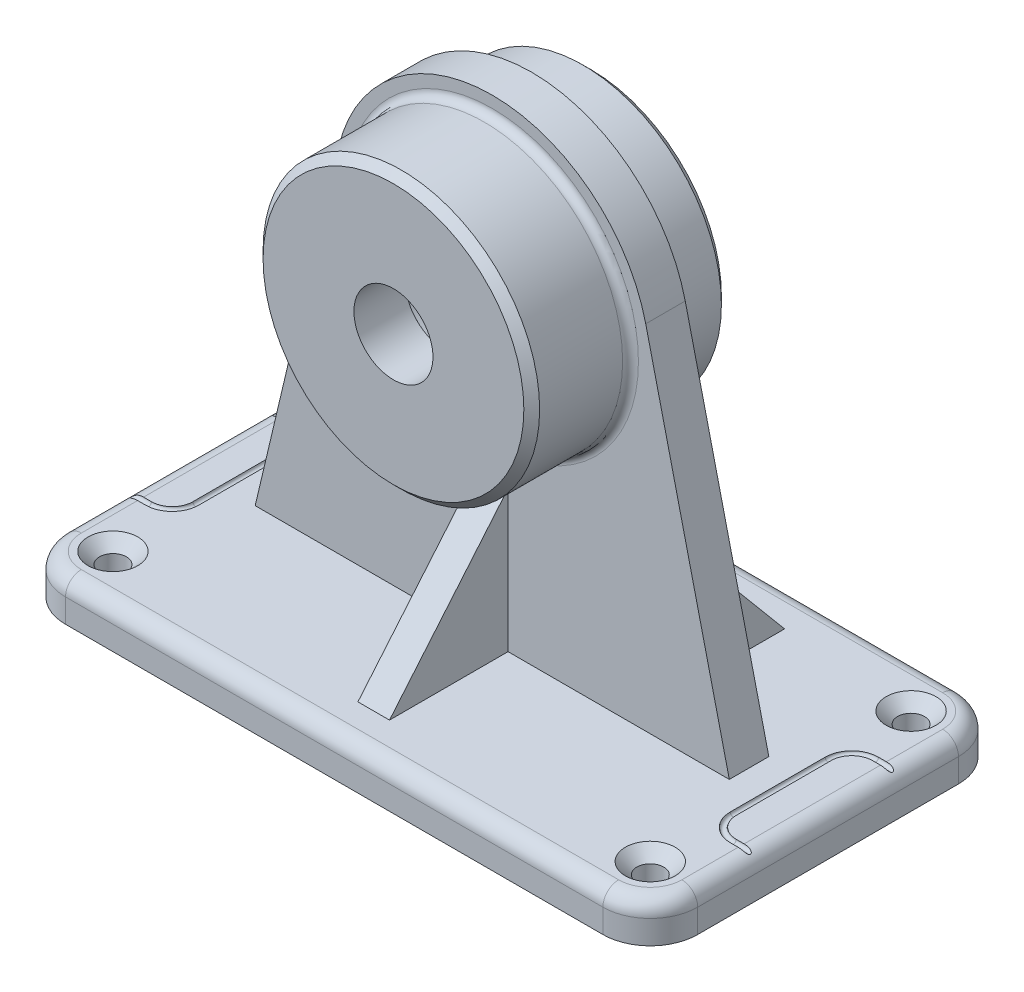
SolidWorks part; units mm, degrees
ref_plane "Front Plane" through (0, 0, 0) normal (0, 0, 1) x (1, 0, 0)
ref_plane "Top Plane" through (0, 0, 0) normal (0, 1, 0) x (1, 0, 0)
ref_plane "Right Plane" through (0, 0, 0) normal (1, 0, 0) x (0, 0, -1)
sketch "Sketch1" plane through (0, 0, 0) normal (0, 1, 0) x (1, 0, 0)
  line L1 (40, -22.5) -> (-40, -22.5)
  line L2 (40, -22.5) -> (40, 22.5)
  line L3 (40, 22.5) -> (-40, 22.5)
  line L4 (-40, -22.5) -> (-40, 22.5)
  line L5 (40, -22.5) -> (-40, 22.5) construction
  line L6 (40, 22.5) -> (-40, -22.5) construction
  point P0 (0, 0)
  dimension "D1" = 80
  dimension "D2" = 45
extrude "Boss-Extrude1" add sketch "Sketch1" along normal blind 5
sketch "Sketch2" plane through (0, 5, 0) normal (0, 1, 0) x (1, 0, 0)
  line L0 (7, 10.5) -> (-7, 10.5) construction
  line L1 (7, 7.5) -> (-7, 7.5)
  line L2 (7, 13.5) -> (-7, 13.5)
  arc A0 (7, 7.5) -> (7, 13.5) centre (7, 10.5) ccw
  arc A1 (-7, 13.5) -> (-7, 7.5) centre (-7, 10.5) ccw
  point P2 (0, 10.5)
  dimension "D3" = 3
  dimension "D1" = 10.5
  dimension "D2" = 14
extrude "Cut-Extrude1" cut sketch "Sketch2" against normal blind 5
fillet "Fillet1" radius 6 1 edges at (-40, 2.5, -22.5)
fillet "Fillet2" radius 6 1 edges at (-40, 2.5, 22.5)
fillet "Fillet3" radius 6 1 edges at (40, 2.5, 22.5)
fillet "Fillet4" radius 6 1 edges at (40, 2.5, -22.5)
sketch "Sketch3" plane through (0, 5, 0) normal (0, 1, 0) x (1, 0, 0)
  line L0 (40, -9) -> (37, -9)
  line L1 (40, -16.5) -> (40, 16.5) construction
  line L2 (34, -6) -> (34, 6)
  line L3 (37, 9) -> (40, 9)
  line L4 (34, 0) -> (45.2259, 0) construction
  arc A0 (37, -9) -> (34, -6) centre (37, -6) cw
  arc A1 (37, 9) -> (34, 6) centre (37, 6) ccw
  dimension "D4" = 3
  dimension "D1" = 13.5
  dimension "D2" = 6
sweep "Cut-Sweep1" cut path "Sketch3" circular profile diameter 0.75 parameters "D3"=0.75
mirror "Mirror1" about plane through (0, 0, 0) normal (1, 0, 0) of "Cut-Sweep1"
fillet "Fillet5" radius 2 8 edges at (38.2426, 5, -20.7426) (-38.2426, 5, -20.7426) (-40, 5, 12.9375) (-38.2426, 5, 20.7426) (40, 5, 12.9375) (38.2426, 5, 20.7426) (0, 5, -22.5) (0, 5, 22.5)
sketch "Sketch17" plane through (0, 5, 0) normal (0, 1, 0) x (1, 0, 0)
  point P0 (34, 16.5)
  point P1 (34, -16.5)
  point P3 (-34, -16.5)
  point P5 (-34, 16.5)
hole_wizard "CSK for M3 Countersunk Flat Head Screw1" positions "Sketch17" profile "Sketch18" countersink size "M3" standard "ISO" end condition through all
sketch "Sketch18" plane through (34, 5, -16.5) normal (1, 0, 0) x (0, 0, 1)
  line L0 (0, 0) -> (0, 5)
  line L1 (0, 5) -> (1.7, 5)
  line L2 (1.7, 5) -> (1.7, 1.45)
  line L3 (1.7, 1.45) -> (3.15, 0)
  line L5 (3.15, 0) -> (0, 0)
  line L6 (-1.7, 1.45) -> (-3.15, 0) construction
  line L11 (0, -6.35) -> (0, 107.95) construction
  dimension "Thru Hole Dia." = 3.4
  dimension "Thru Hole Depth" = 5
  dimension "Near C'Sink Dia." = 6.3
  dimension "Near C'Sink Angle" = 90
chamfer "Chamfer2" distance 2 angle 45 4 edges at (0, 5, -7.5) (10, 5, -10.5) (-10, 5, -10.5) (0, 5, -13.5)
sketch "Sketch19" plane through (0, 0, 0) normal (0, 0, 1) x (1, 0, 0)
  line L0 (0, 5) -> (-30, 5)
  line L1 (-34, 5) -> (34, 5) construction
  line L2 (0, 5) -> (30, 5)
  line L4 (-19.4224, 49.6418) -> (-30, 5)
  line L5 (19.4224, 49.6418) -> (30, 5)
  line L6 (-34, 0) -> (34, 0) construction
  arc A0 (-19.4224, 49.6418) -> (19.4224, 49.6418) centre (0, 45.0398) cw
  point P8 (0, 65)
  dimension "D1" = 30
  dimension "D2" = 60
  dimension "D3" = 65
  dimension "D4" = 76.67
  dimension "D5" = 76.67
extrude "Boss-Extrude2" add sketch "Sketch19" along normal mid plane 5
sketch "Sketch20" plane through (0, 0, 2.5) normal (0, 0, 1) x (1, 0, 0)
  circle A0 centre (0, 45.0398) radius 17.5
  dimension "D1" = 35
extrude "Boss-Extrude3" add sketch "Sketch20" along normal mid plane 25
chamfer "Chamfer3" distance 1 angle 45 2 edges at (17.5, 45.0398, -10) (17.5, 45.0398, 15)
fillet "Fillet6" radius 1 2 edges at (-17.5, 45.0398, -2.5) (-17.5, 45.0398, 2.5)
sketch "Sketch21" plane through (0, 0, 0) normal (1, 0, 0) x (0, 0, -1)
  line L0 (-17.5, 5) -> (-2.5, 22.8763)
  line L1 (-16.5, 5) -> (-9.375, 5) construction
  line L2 (-2.5, 5) -> (-2.5, 49.6418) construction
  line L3 (-8.625, 5) -> (8.625, 5) construction
  dimension "D1" = 15
  dimension "D2" = 50
rib "Rib1" sketch "Sketch21" sketch "Sketch21" thickness 4 extrusion direction parallel to sketch draft on no parameters "D1"=4
ref_plane "Plane1" through (15, 0, 0) normal (1, 0, 0) x (0, 0, -1)
sketch "Sketch22" plane through (15, 0, 0) normal (1, 0, 0) x (0, 0, -1)
  line L0 (17.5, 5) -> (2.5, 22.8763)
  line L1 (9.375, 5) -> (16.5, 5) construction
  line L2 (2.5, 5) -> (2.5, 49.6418) construction
  dimension "D1" = 15
  dimension "D2" = 50
rib "Rib2" sketch "Sketch22" sketch "Sketch22" thickness 4 extrusion direction parallel to sketch draft on no parameters "D1"=4
mirror "Mirror2" about plane through (0, 0, 0) normal (1, 0, 0) of "Rib2"
sketch "Sketch23" plane through (0, 0, 0) normal (1, 0, 0) x (0, 0, -1)
  line L0 (10, 45.0398) -> (10, 55.0398)
  line L1 (10, 28.5398) -> (10, 61.5398) construction
  line L2 (10, 45.0398) -> (-15, 45.0398)
  line L3 (-15, 61.5398) -> (-15, 28.5398) construction
  line L4 (-15, 45.0398) -> (-15, 50.0398)
  line L5 (-15, 50.0398) -> (-8.5, 50.0398)
  line L6 (-8.5, 50.0398) -> (-6.3994, 53.0398)
  line L7 (-6.3994, 53.0398) -> (4.0006, 53.0398)
  line L8 (10, 55.0398) -> (4.0006, 55.0398)
  line L9 (4.0006, 55.0398) -> (4.0006, 53.0398)
  dimension "D1" = 10
  dimension "D2" = 5
  dimension "D3" = 6.5
  dimension "D4" = 125
  dimension "D5" = 8
  dimension "D6" = 10.4
revolve "Cut-Revolve1" cut sketch "Sketch23" angle 360 about L2
